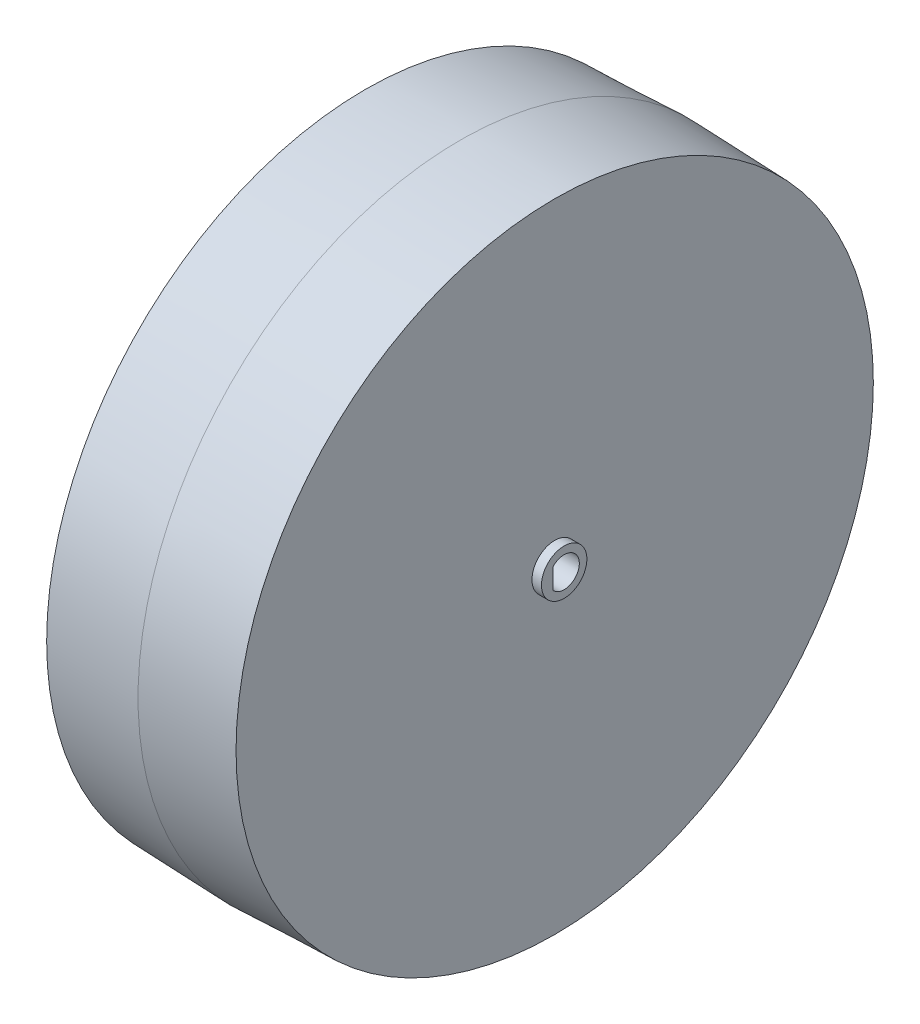
SolidWorks part; units mm, degrees
note: '?' marks a value the reader was unsure of.
ref_plane "Front Plane" through (0, 0, 0) normal (0, 0, 1) x (1, 0, 0)
ref_plane "Top Plane" through (0, 0, 0) normal (0, 1, 0) x (1, 0, 0)
ref_plane "Right Plane" through (0, 0, 0) normal (1, 0, 0) x (0, 0, -1)
sketch "Sketch1" plane through (0, 0, 0) normal (1, 0, 0) x (0, 0, -1)
  circle A0 centre (0, 0) radius 85
  dimension "D1" = 170
extrude "Boss-Extrude1" add sketch "Sketch1" along normal mid plane 50 draft 2
sketch "Sketch2" plane through (25, 0, 0) normal (1, 0, 0) x (0, 0, -1)
  circle A0 centre (0, 0) radius 6
  dimension "D1" = 12
extrude "Boss-Extrude2" add sketch "Sketch2" along normal blind 2.5
sketch "Sketch3" plane through (27.5, 0, 0) normal (1, 0, 0) x (0, 0, -1)
  line L4 (-3, -2.6458) -> (-3, 2.6458)
  arc A0 (-3, -2.6458) -> (-3, 2.6458) centre (0, 0) ccw
  dimension "D1" = 8
extrude "Cut-Extrude1" cut sketch "Sketch3" against normal blind 14
ref_axis "Axis1" through (36.5699, 0, 0) along (-1, 0, 0)?
